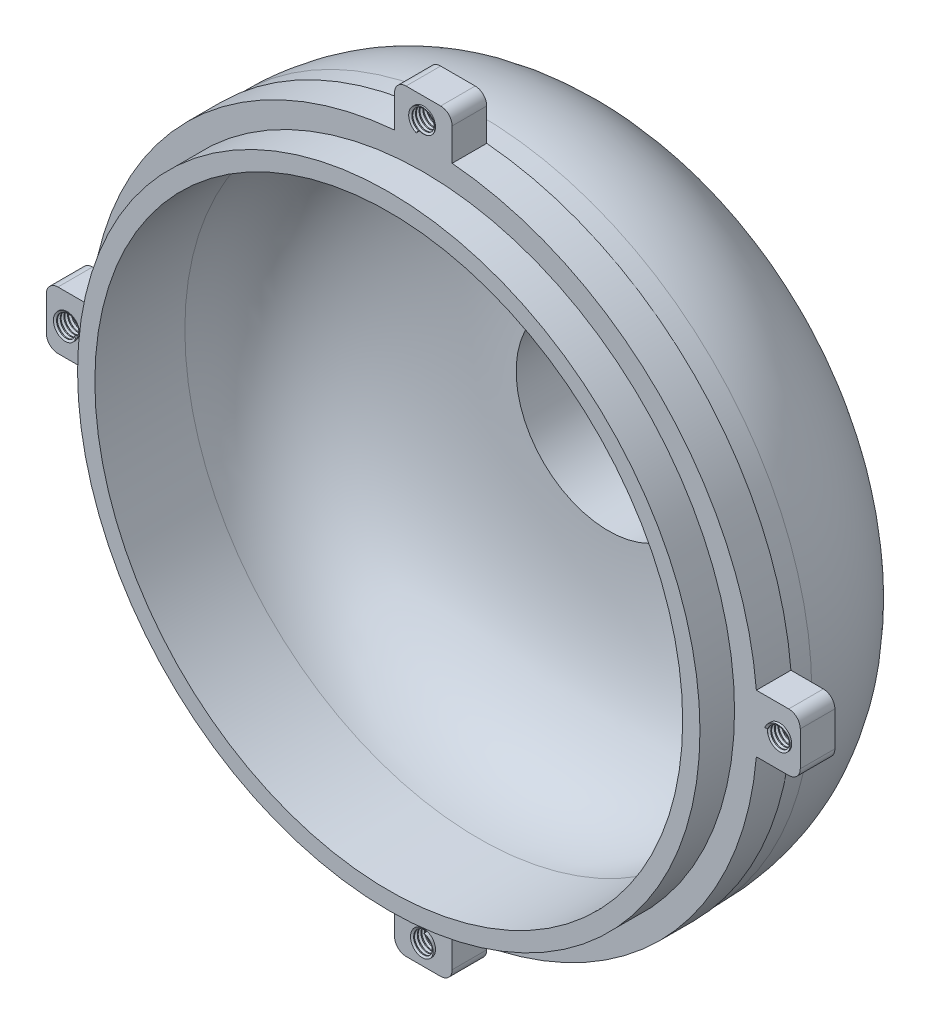
SolidWorks part; units mm, degrees
ref_plane "Front Plane" through (0, 0, 0) normal (0, 0, 1) x (1, 0, 0)
ref_plane "Top Plane" through (0, 0, 0) normal (0, 1, 0) x (1, 0, 0)
ref_plane "Right Plane" through (0, 0, 0) normal (1, 0, 0) x (0, 0, -1)
sketch "Sketch1" plane through (0, 0, 0) normal (0, 0, 1) x (1, 0, 0)
  circle A0 centre (0, 0) radius 29
  circle A1 centre (0, 0) radius 27
  dimension "D1" = 58
  dimension "D2" = 54
extrude "Boss-Extrude1" add sketch "Sketch1" along normal blind 3
sketch "Sketch2" plane through (0, 0, 0) normal (0, 0, 1) x (1, 0, 0)
  circle A0 centre (0, 0) radius 25.5
  circle A1 centre (0, 0) radius 27 construction
  circle A2 centre (0, 0) radius 27
  dimension "D1" = 1.5
extrude "Boss-Extrude2" add sketch "Sketch2" along normal blind 6
sketch "Sketch3" plane through (0, 0, 0) normal (0, 0, 1) x (1, 0, 0)
  line L1 (27.25, 2.5) -> (32.7, 2.5)
  line L2 (32.7, 2.5) -> (32.7, -2.5)
  line L3 (32.7, -2.5) -> (27.25, -2.5)
  line L4 (27.25, -2.5) -> (27.25, 2.5)
  line L5 (29, 0) -> (25.5, 0) construction
  circle A2 centre (0, 0) radius 29 construction
  circle A3 centre (0, 0) radius 25.5 construction
  point P14 (27.25, 0)
  point P15 (27.25, 0)
  dimension "D1" = 5
  dimension "D2" = 5.45
extrude "Boss-Extrude3" add sketch "Sketch3" along normal blind 3
fillet "Fillet1" radius 1 2 edges at (32.7, -2.5, 1.5) (32.7, 2.5, 1.5)
sketch "Sketch4" plane through (0, 0, 0) normal (0, 0, -1) x (-1, 0, 0)
  line L0 (-32.7, -1.5) -> (-32.7, 1.5) construction
  circle A0 centre (-30.9, 0) radius 1.055
  dimension "D1" = 2.11
  dimension "D2" = 1.8
extrude "Cut-Extrude1" cut sketch "Sketch4" against normal blind 3
thread "Thread1" pitch 0.3175 method extrude profile "Thread Profile1" start angle 0, offset 0, length 0, pitch 0.3175, diameter 2.11
ref_plane "Plane1" through (31.955, 0, 0) normal (0, -1, 0) x (1, 0, 0)
sketch "Thread Profile1" plane through (31.955, 0, 0) normal (0, -1, 0) x (1, 0, 0)
  line L0 (0, 0) -> (0, 0.3175) construction
  line L11 (0, 0) -> (0, 0.2778)
  line L12 (0, 0.2778) -> (-0.1719, 0.1786)
  line L13 (-0.1719, 0.1786) -> (-0.1719, 0.0992)
  line L15 (-0.1719, 0.0992) -> (0, 0)
  line L17 (-0.1719, 0.1389) -> (0, 0.1389) construction
  point P2 (0, 0)
  dimension "Pitch" = 0.3175
  dimension "Profile_Angle" = 60
  dimension "Profile_Land" = 0.0794
  dimension "Profile_Height" = 0.1719
sketch "Sketch7" plane through (0, 0, 0) normal (1, 0, 0) x (0, 0, -1)
  line L0 (-25.5048, 0) -> (14.3861, 0) construction
pattern_circular "CirPattern1" count 4 over 360 about axis through (0, 0, 25.5048) along (0, 0, -1) of "Boss-Extrude3", "Fillet1", "Cut-Extrude1", "Thread1"
sketch "Sketch8" plane through (0, 0, 0) normal (1, 0, 0) x (0, 0, -1)
  line L0 (0, 28.892) -> (1.8081, 28.892)
  line L1 (0, 25.5) -> (1.8081, 25.5)
  line L2 (1.8081, 25.5) -> (13.0527, 25.7921) construction
  line L3 (13.0527, 25.7921) -> (13.0527, 8) construction
  line L5 (1.8081, 28.892) -> (16.3439, 28.892) construction
  line L6 (16.3439, 28.892) -> (17.8527, 8) construction
  line L7 (13.0527, 8) -> (17.8527, 8)
  line L8 (0, 28.892) -> (0, 25.5)
  line L10 (-25.5048, 0) -> (14.3861, 0) construction
  spline S0 degree 2 poles (1.8081, 25.5) (13.0527, 25.7921) (13.0527, 8) knots 0 0 0 1 1 1
  spline S1 degree 2 poles (1.8081, 28.892) (16.3439, 28.892) (17.8527, 8) knots 0 0 0 1 1 1
  dimension "D1" = 8
  dimension "D2" = 4.8
revolve "Revolve1" add sketch "Sketch8" angle 360 about L0
